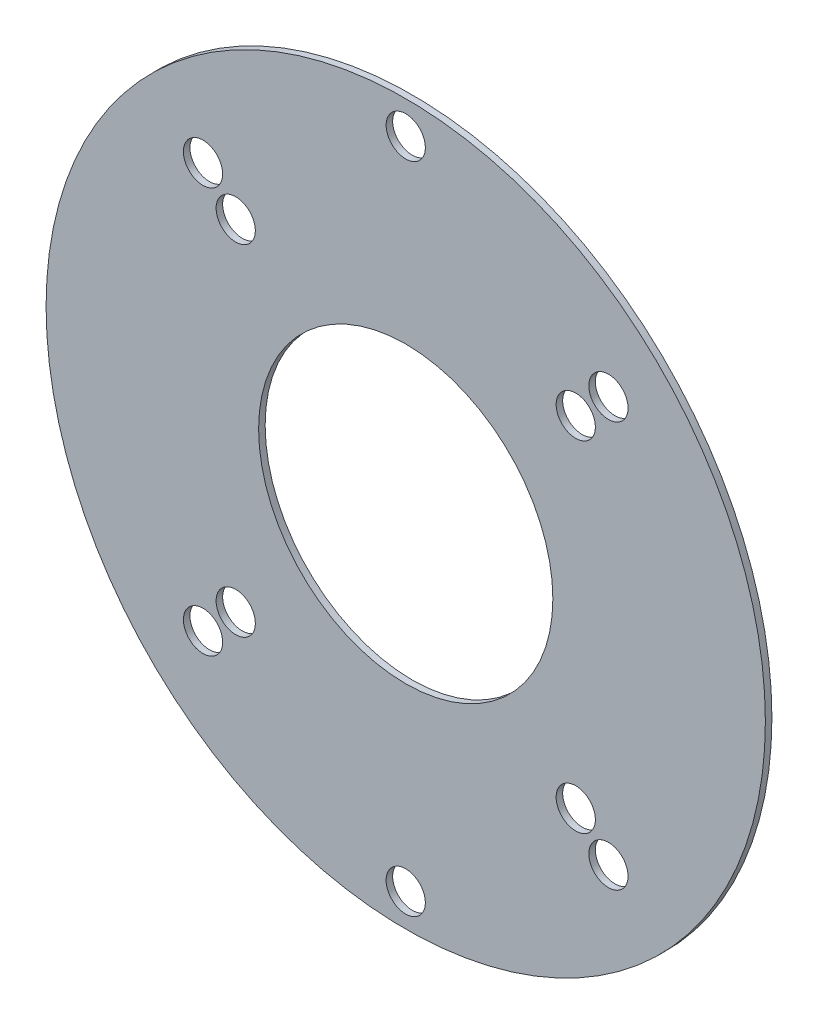
SolidWorks part; units mm, degrees
ref_plane "Front Plane" through (0, 0, 0) normal (0, 0, 1) x (1, 0, 0)
ref_plane "Top Plane" through (0, 0, 0) normal (0, 1, 0) x (1, 0, 0)
ref_plane "Right Plane" through (0, 0, 0) normal (1, 0, 0) x (0, 0, -1)
sketch "Croquis1" plane through (0, 0, 0) normal (0, 0, 1) x (1, 0, 0)
  circle A0 centre (0, 0) radius 27.5
  dimension "D1" = 55
sheet metal parameters "Chapa metálica1" thickness 0.5 parameters "D1"=0.5, "Espesor"=0.5
base flange "Brida base1" sketch "Croquis1" thickness 0.5 reverse thickness direction no parameters "D1"=0.5
sketch "Croquis6" plane through (0, 0, 0) normal (0, 0, 1) x (1, 0, 0)
  line L0 (0, 29.4175) -> (0, -29.5287) construction
  line L1 (-30.6965, 0) -> (34.2555, 0) construction
  circle A0 centre (-15.5, 15.5) radius 1.5
  circle A1 centre (15.5, 15.5) radius 1.5
  circle A2 centre (-15.5, 15.5) radius 1.5
  circle A3 centre (15.5, 15.5) radius 1.5
  circle A4 centre (15.5, -15.5) radius 1.5
  circle A5 centre (-15.5, -15.5) radius 1.5
  circle A6 centre (-13, 13) radius 1.5
  circle A7 centre (13, 13) radius 1.5
  circle A8 centre (13, -13) radius 1.5
  circle A9 centre (-13, -13) radius 1.5
  circle A10 centre (0, 0) radius 11.25
  circle A11 centre (0, 25) radius 1.5
  circle A12 centre (0, -25) radius 1.5
  dimension "D1" = 3
  dimension "D2" = 31
  dimension "D4" = 3
  dimension "D7" = 22.5
  dimension "D8" = 3
  dimension "D3" = 31
  dimension "D5" = 26
  dimension "D6" = 26
  dimension "D9" = 25
extrude "Cortar-Extruir3" cut sketch "Croquis6" against normal blind 10 contours A10 | A6 | A9 | A7 | A11 | A0 | A5 | A12 | A8 | A4 | A1 region at (-13, 13, 0) region at (13, 13, 0) region at (-13, -13, 0) region at (0, 0, 0) region at (0, 25, 0) normal cut yes
flat pattern "Chapa desplegada1" [suppressed]
sketch "Líneas de pliegue1" plane through (0, 0, 0) normal (0, 1, 0) x (-1, 0, 0)
sketch3d "Cuadro delimitador1" [suppressed]
  line L0 (25.6675, -29.205, 0) -> (-29.1958, -25.6779, 0) construction
  line L1 (29.194, 25.6499, 0) -> (-25.6693, 29.1769, 0) construction
  line L2 (25.6675, -29.205, 0) -> (29.194, 25.6499, 0) construction
  line L3 (-29.1958, -25.6779, 0) -> (-25.6693, 29.1769, 0) construction
